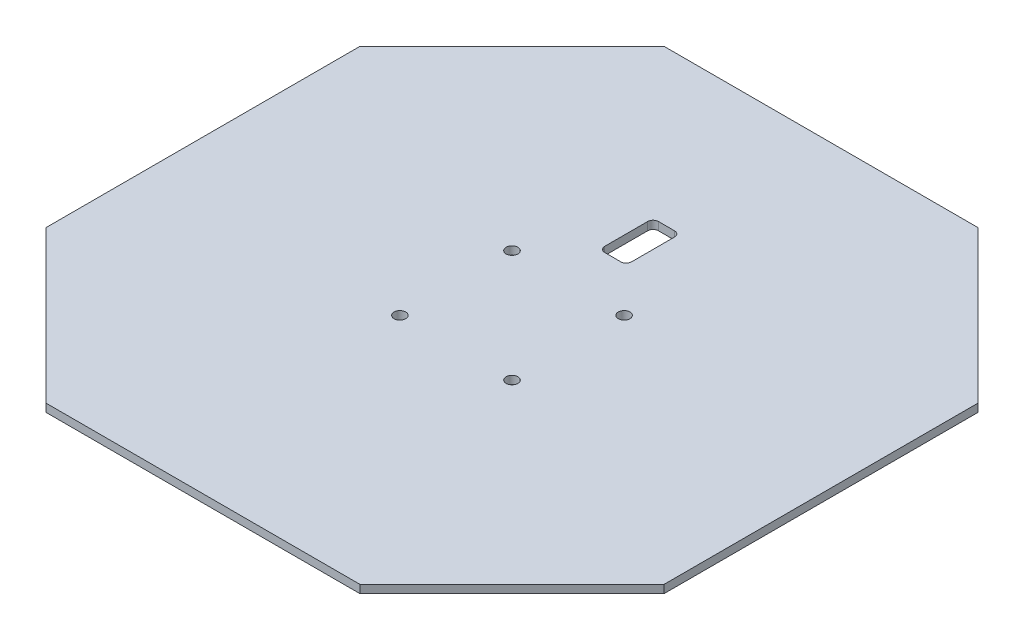
SolidWorks part; units mm, degrees
ref_plane "Front Plane" through (0, 0, 0) normal (0, 0, 1) x (1, 0, 0)
ref_plane "Top Plane" through (0, 0, 0) normal (0, 1, 0) x (1, 0, 0)
ref_plane "Right Plane" through (0, 0, 0) normal (1, 0, 0) x (0, 0, -1)
sketch "Sketch1" plane through (0, 0, 0) normal (0, 1, 0) x (1, 0, 0)
  line L1 (0, 0) -> (230, 0)
  line L2 (0, 0) -> (0, 230)
  line L3 (0, 230) -> (230, 230)
  line L4 (230, 0) -> (230, 230)
  dimension "D1" = 230
  dimension "D2" = 230
extrude "Boss-Extrude1" add sketch "Sketch1" along normal blind 3
fillet "Chamfer2" radius 56.5685 1 edges at (0, 1.5, 0) type face fillet profile chamfer first side face at (115, 1.5, 0) second side face at (0, 1.5, -115)
fillet "Chamfer3" radius 56.5685 1 edges at (0, 1.5, -230) type face fillet profile chamfer first side face at (0, 1.5, -143.2843) second side face at (115, 1.5, -230)
fillet "Chamfer4" radius 56.5685 1 edges at (230, 1.5, -230) type face fillet profile chamfer first side face at (143.2842, 1.5, -230) second side face at (230, 1.5, -115)
fillet "Chamfer5" radius 56.5685 1 edges at (230, 1.5, 0) type face fillet profile chamfer first side face at (230, 1.5, -86.7158) second side face at (143.2843, 1.5, 0)
hole_wizard "11/64 (0.17188) Diameter Hole1" positions "Sketch4" profile "Sketch3" hole size "11/64" standard "ANSI Inch" end condition up to next
sketch "Sketch4" plane through (0, 3, 0) normal (0, 1, 0) x (1, 0, 0)
  point P0 (94.1403, 135.8597)
  point P3 (135.8597, 135.8597)
  point P6 (135.8597, 94.1403)
  point P9 (94.1403, 94.1403)
  point P12 (0, 0)
  point P13 (0, 0)
  point P14 (0, 0)
  point P15 (0, 0)
sketch "Sketch3" plane through (94.1403, 3, -135.8597) normal (1, 0, 0) x (0, 0, 1)
  line L0 (0, 0) -> (0, 3)
  line L1 (0, 3) -> (2.1829, 3)
  line L2 (2.1829, 3) -> (2.1829, 0)
  line L5 (2.1829, 0) -> (0, 0)
  line L11 (0, -6.35) -> (0, 107.95) construction
  dimension "Thru Hole Dia." = 4.3658
  dimension "Thru Hole Depth" = 3
sketch "Sketch11" plane through (0, 3, 0) normal (0, 1, 0) x (1, 0, 0)
  line L0 (230, 115) -> (0, 115) construction
  line L1 (230, 56.5685) -> (230, 173.4315) construction
  line L2 (0, 173.4315) -> (0, 56.5685) construction
  line L4 (115, 115) -> (115, 152.5) construction
  line L5 (115, 152.5) -> (120, 152.5)
  line L6 (115, 152.5) -> (110, 152.5)
  line L7 (120, 152.5) -> (120, 172.5)
  line L8 (120, 172.5) -> (110, 172.5)
  line L9 (110, 152.5) -> (110, 172.5)
extrude "Cut-Extrude3" cut sketch "Sketch11" against normal through all
fillet "Fillet9" radius 2 1 edges at (120, 1.5, -172.5) type face fillet first side face at (120, 1.5, -162.5) second side face at (115, 1.5, -172.5)
fillet "Fillet10" radius 2 1 edges at (110, 1.5, -172.5) type face fillet first side face at (114, 1.5, -172.5) second side face at (110, 1.5, -162.5)
fillet "Fillet11" radius 2 1 edges at (120, 1.5, -152.5) type face fillet first side face at (120, 1.5, -161.5) second side face at (115, 1.5, -152.5)
fillet "Fillet12" radius 2 1 edges at (110, 1.5, -152.5) type face fillet first side face at (114, 1.5, -152.5) second side face at (110, 1.5, -161.5)
